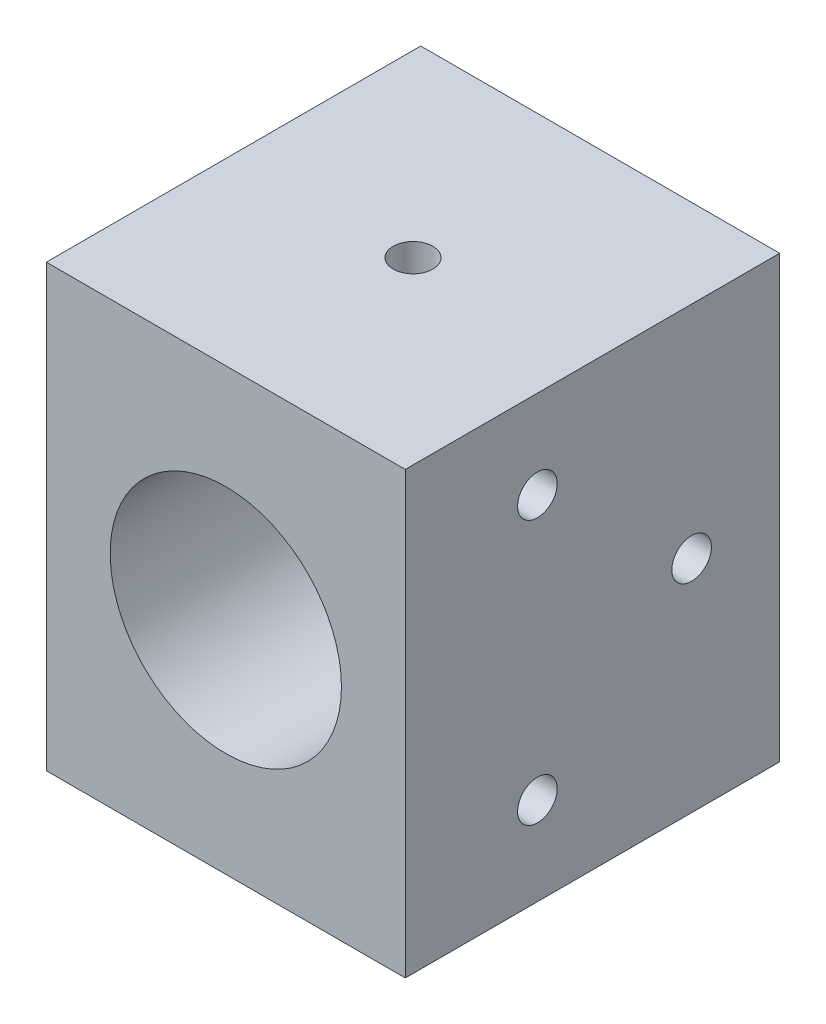
SolidWorks part; units mm, degrees
ref_plane "前视基准面" through (0, 0, 0) normal (0, 0, 1) x (1, 0, 0)
ref_plane "上视基准面" through (0, 0, 0) normal (0, 1, 0) x (1, 0, 0)
ref_plane "右视基准面" through (0, 0, 0) normal (1, 0, 0) x (0, 0, -1)
other "Configuration Table"
sketch "草图1" plane through (0, 0, 0) normal (0, 0, 1) x (1, 0, 0)
  line L0 (-8.15, 10) -> (8.15, -10) construction
  line L9 (-8.15, 10) -> (8.15, 10)
  line L10 (-8.15, 10) -> (-8.15, -10)
  line L11 (-8.15, -10) -> (8.15, -10)
  line L12 (8.15, 10) -> (8.15, -10)
  circle A12 centre (0, 0) radius 5.25
  dimension "D1" = 10.5
  dimension "D2" = 16.3
  dimension "D3" = 20
extrude "凸台-拉伸1" add sketch "草图1" along normal blind 10
extrude "凸台-拉伸2" add sketch "草图1<6>" against normal blind 2 contours L12 L11 L10 L9
sketch "草图1<6>" plane through (0, 0, 0) normal (0, 0, 1) x (1, 0, 0) same geometry as "草图1"
sketch "草图2" plane through (-8.15, 0, 0) normal (-1, 0, 0) x (0, 0, 1)
  line L0 (10, 10) -> (-2, 10) construction
  line L1 (10, -10) -> (-2, -10) construction
  circle A0 centre (4, 6) radius 0.9
  circle A1 centre (4, -6) radius 0.9
  point P8 (4, 10)
  dimension "D3" = 1.8
  dimension "D1" = 4
  dimension "D2" = 4
extrude "切除-拉伸1" cut sketch "草图2" against normal blind 4
extrude "切除-拉伸2" cut sketch "草图2<2>" along normal blind 4 from surface starting at face at (8.15, 0, 4)
sketch "草图2<2>" plane through (-8.15, 0, 0) normal (-1, 0, 0) x (0, 0, 1) same geometry as "草图2"
sketch "草图3" plane through (8.15, 0, 0) normal (1, 0, 0) x (0, 0, -1)
  line L0 (2, 10) -> (2, -10) construction
  line L1 (2, 10) -> (7, 10)
  line L2 (2, 10) -> (2, -10)
  line L3 (2, -10) -> (7, -10)
  line L4 (7, 10) -> (7, -10)
  line L5 (-10, 10) -> (2, 10) construction
  dimension "D1" = 5
extrude "凸台-拉伸3" add sketch "草图3" against normal up to surface (16.3 mm away) up to face at (-8.15, 5.1, 4)
sketch "草图5" plane through (-8.15, 0, 0) normal (-1, 0, 0) x (0, 0, 1)
  circle A0 centre (-3, 0) radius 0.9
  circle A1 centre (4, 6) radius 0.9 construction
  circle A2 centre (4, -6) radius 0.9 construction
  dimension "D1" = 7
extrude "切除-拉伸3" cut sketch "草图5" against normal through all
sketch "草图6" plane through (0, -10, 0) normal (0, -1, 0) x (1, 0, 0)
  line L0 (-8.15, 10) -> (-8.15, -7) construction
  line L1 (-8.15, 1.5) -> (8.15, 1.5)
  line L2 (8.15, 10) -> (8.15, -7) construction
  circle A0 centre (0, 1.5) radius 0.9
  point P9 (0, 0)
  dimension "D1" = 1.8
extrude "切除-拉伸4" cut sketch "草图6" against normal blind 4 contours A0
extrude "切除-拉伸5" cut sketch "草图6<3>" along normal blind 4 from surface contours A0 starting at face at (0, 10, 1.5)
sketch "草图6<3>" plane through (0, -10, 0) normal (0, -1, 0) x (1, 0, 0) same geometry as "草图6"
